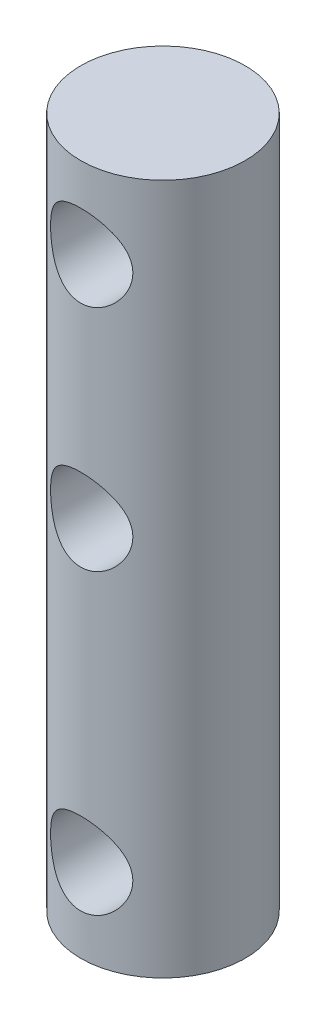
SolidWorks part; units mm, degrees
ref_plane "Front Plane" through (0, 0, 0) normal (0, 0, 1) x (1, 0, 0)
ref_plane "Top Plane" through (0, 0, 0) normal (0, 1, 0) x (1, 0, 0)
ref_plane "Right Plane" through (0, 0, 0) normal (1, 0, 0) x (0, 0, -1)
sketch "Sketch1" plane through (0, 0, 0) normal (0, 1, 0) x (1, 0, 0)
  circle A0 centre (0, 0) radius 2.5
  dimension "D1" = 5
extrude "Boss-Extrude1" add sketch "Sketch1" along normal blind 21
sketch "Sketch2" plane through (0, 0, 0) normal (0, 0, 1) x (1, 0, 0)
  line L0 (-2.5, 0) -> (2.5, 0) construction
  line L1 (2.5, 21) -> (-2.5, 21) construction
  circle A0 centre (0, 18.5) radius 1.25
  circle A1 centre (0, 2.5) radius 1.25
  circle A2 centre (0, 11.55) radius 1.25
  point P4 (0, 0)
  dimension "D1" = 2.5
  dimension "D4" = 11.55
  dimension "D2" = 2.5
  dimension "D3" = 2.5
extrude "Cut-Extrude1" cut sketch "Sketch2" against normal through all both and the other way through all
